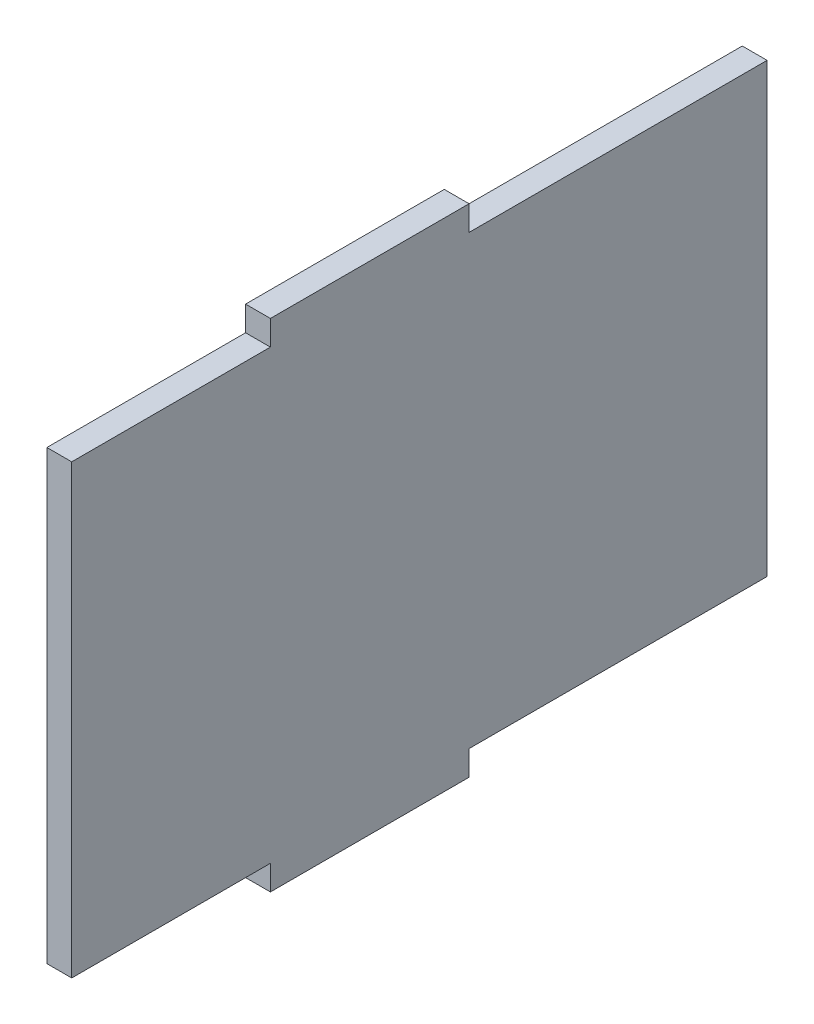
SolidWorks part; units mm, degrees
ref_plane "Front Plane" through (0, 0, 0) normal (0, 0, 1) x (1, 0, 0)
ref_plane "Top Plane" through (0, 0, 0) normal (0, 1, 0) x (1, 0, 0)
ref_plane "Right Plane" through (0, 0, 0) normal (1, 0, 0) x (0, 0, -1)
sketch "Sketch1" plane through (0, 0, 0) normal (1, 0, 0) x (0, 0, -1)
  line L1 (-44.45, -31.75) -> (44.45, -31.75)
  line L2 (-44.45, -31.75) -> (-44.45, 31.75)
  line L3 (-44.45, 31.75) -> (44.45, 31.75)
  line L4 (44.45, -31.75) -> (44.45, 31.75)
  line L5 (-44.45, -31.75) -> (44.45, 31.75) construction
  line L6 (-44.45, 31.75) -> (44.45, -31.75) construction
  point P0 (0, 0)
  dimension "D1" = 88.9
  dimension "D2" = 63.5
extrude "Boss-Extrude1" add sketch "Sketch1" along normal blind 3.175
sketch "Sketch2" plane through (3.175, 0, 0) normal (1, 0, 0) x (0, 0, -1)
  line L0 (-44.45, -31.75) -> (44.45, -31.75) construction
  line L1 (-44.45, -31.75) -> (44.45, -31.75) construction
  line L2 (-19.05, -31.75) -> (-19.05, -28.575) construction
  line L3 (-19.05, 31.75) -> (-19.05, 28.575) construction
  line L4 (44.45, -31.75) -> (6.35, -31.75)
  line L5 (-44.45, 0) -> (44.45, 0) construction
  line L6 (-44.45, 31.75) -> (-44.45, -31.75) construction
  line L7 (44.45, -31.75) -> (44.45, 31.75) construction
  line L8 (44.45, -31.75) -> (44.45, -28.575)
  line L9 (44.45, -28.575) -> (6.35, -28.575)
  line L10 (6.35, -31.75) -> (6.35, -28.575)
  line L11 (-19.05, 28.575) -> (-44.45, 28.575)
  line L12 (0, 31.75) -> (0, -31.75) construction
  line L13 (-19.05, 31.75) -> (-19.05, 28.575)
  line L14 (-19.05, 31.75) -> (-41.275, 31.75)
  line L15 (-44.45, 31.75) -> (-44.45, 28.575)
  line L16 (-44.45, 31.75) -> (-41.275, 31.75)
  line L17 (-44.45, -31.75) -> (-41.275, -31.75)
  line L18 (-44.45, -31.75) -> (-44.45, -28.575)
  line L19 (6.35, 31.75) -> (6.35, 28.575)
  line L20 (44.45, 28.575) -> (6.35, 28.575)
  line L21 (44.45, 31.75) -> (-44.45, 31.75) construction
  line L22 (44.45, 31.75) -> (44.45, 28.575)
  line L23 (44.45, 31.75) -> (6.35, 31.75)
  line L31 (-19.05, -31.75) -> (-41.275, -31.75)
  line L32 (-19.05, -31.75) -> (-19.05, -28.575)
  line L33 (-19.05, -28.575) -> (-44.45, -28.575)
  point P6 (0, -31.75)
  dimension "D1" = 3.175
  dimension "D2" = 19.05
  dimension "D3" = 25.4
extrude "Cut-Extrude1" cut sketch "Sketch2" against normal through all
